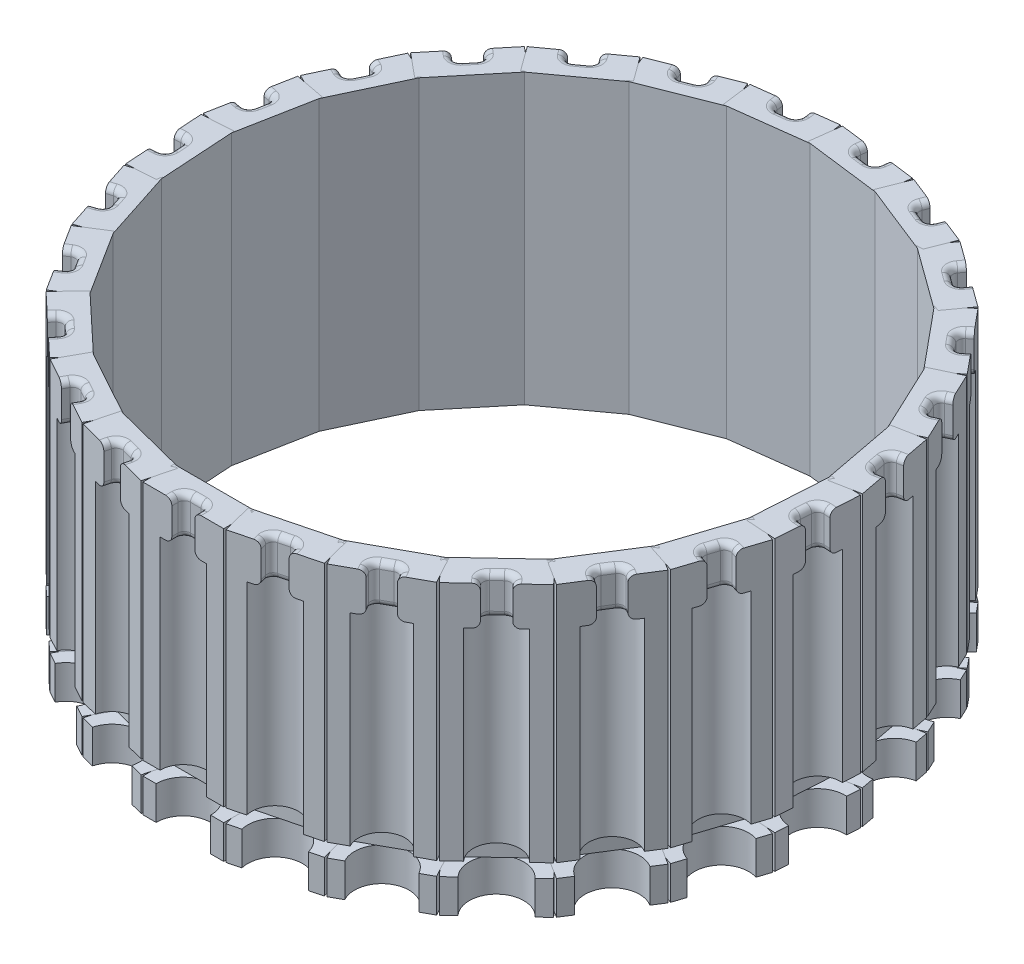
SolidWorks part; units mm, degrees
material "Plain Carbon Steel"
ref_plane "Front Plane" through (0, 0, 0) normal (1, 0, 0) x (0, 1, 0)
ref_plane "Top Plane" through (0, 0, 0) normal (0, 0, 1) x (0, 1, 0)
ref_plane "Right Plane" through (0, 0, 0) normal (0, 1, 0) x (-1, 0, 0)
other "Center of Mass"
sketch "Sketch1" plane through (0, 0, 0) normal (0, 0, 1) x (0, 1, 0)
  line L1 (-75, -150) -> (75, -150)
  line L2 (-75, -150) -> (-75, 150)
  line L3 (-75, 150) -> (75, 150)
  line L4 (75, -150) -> (75, 150)
  line L5 (-75, -150) -> (75, 150) construction
  line L6 (-75, 150) -> (75, -150) construction
  point P0 (0, 0)
  dimension "D1" = 300
  dimension "D2" = 150
extrude "Boss-Extrude1" add sketch "Sketch1" along normal blind 10
sketch "flange slit" plane through (0, 0, 10) normal (0, 0, 1) x (1, 0, 0)
  line L0 (0, 75) -> (0, -75) construction
  line L1 (150, 75) -> (-150, 75) construction
  line L2 (-150, -75) -> (150, -75) construction
  line L3 (-124, 0) -> (150, 0) construction
  line L5 (150, -75) -> (150, 75) construction
  line L6 (-70.7884, -63.1) -> (-70.7884, -60.9) construction
  line L7 (-150, 75) -> (-124, 75) construction
  line L9 (-150, -75) -> (-124, -75) construction
  line L11 (-70.7884, -63.1) -> (-70.7884, -62) construction
  line L12 (-150, -59.8) -> (-124, -59.8)
  line L13 (-150, -59.8) -> (-150, -64.2)
  line L14 (-150, -64.2) -> (-124, -64.2)
  line L19 (-124, -59.8) -> (-124, -64.2)
  line L20 (-150, -59.8) -> (-124, -64.2) construction
  line L21 (-150, -64.2) -> (-124, -59.8) construction
  line L26 (-70.7884, -62) -> (-150, -62) construction
  point P8 (-137, -62)
  dimension "D1" = 26
  dimension "D2" = 2.2
extrude "Flange Slot" cut sketch "flange slit" against normal blind 8
sketch "Sketch3" plane through (0, 0, 10) normal (0, 0, 1) x (1, 0, 0)
  line L0 (-150, -75) -> (150, -75) construction
  line L1 (-150, 75) -> (-124, 75) construction
  line L2 (-150, 75) -> (-150, -75) construction
  line L3 (-150, -75) -> (-124, -75) construction
  line L4 (-124, 75) -> (-124, -75) construction
  line L5 (-150, 75) -> (-124, -75) construction
  line L6 (-150, -75) -> (-124, 75) construction
  line L7 (-124, -64.2) -> (-124, -59.8) construction
  line L8 (-124, -59.8) -> (-150, -59.8) construction
  line L9 (-144.5, -59.8) -> (-129.5, -59.8)
  line L10 (-144.5, -59.8) -> (-144.5, 5.2)
  line L11 (-144.5, 5.2) -> (-129.5, 5.2)
  line L12 (-129.5, -59.8) -> (-129.5, 5.2)
  line L13 (-144.5, -59.8) -> (-129.5, 5.2) construction
  line L14 (-144.5, 5.2) -> (-129.5, -59.8) construction
  line L15 (-137, 75) -> (-137, -59.8) construction
  line L16 (-137, 5.2) -> (-137, -59.8)
  line L18 (-144.5, 5.2) -> (-137, 5.2)
  line L19 (-144.5, 5.2) -> (-144.5, -59.8)
  line L20 (-144.5, -59.8) -> (-137, -59.8)
  line L21 (-137, 5.2) -> (-137, -59.8)
  line L22 (-144.5, 5.2) -> (-137, -59.8) construction
  line L23 (-144.5, -59.8) -> (-137, 5.2) construction
  point P4 (-137, 0)
  point P14 (-137, -27.3)
  point P23 (-140.75, -27.3)
  dimension "D1" = 65
  dimension "D2" = 15
revolve "Syringe Body Slot" cut sketch "Sketch3" angle 360 about L15 region at (-140.75, -27.3, 10)
sketch "Sketch6" plane through (0, 0, 10) normal (0, 0, 1) x (0, -1, 0)
  line L0 (75, 150) -> (-75, 150) construction
  line L1 (-75, -150) -> (-17.7492, -150)
  line L2 (-75, -150) -> (-75, 150)
  line L3 (-75, 150) -> (-17.7492, 150)
  line L4 (-17.7492, -150) -> (-17.7492, 150)
  line L5 (-75, -150) -> (-17.7492, 150) construction
  line L6 (-75, 150) -> (-17.7492, -150) construction
  point P4 (-46.3746, 0)
extrude "Cut-Extrude2" cut sketch "Sketch6" against normal through all
sketch "Sketch7" plane through (0, 0, 10) normal (0, 0, 1) x (1, 0, 0)
  line L0 (-150, -64.2) -> (-124, -64.2) construction
  line L1 (-137, -64.2) -> (-145.7782, -64.2)
  line L2 (-137, -64.2) -> (-137, -75)
  line L3 (-137, -75) -> (-145.7782, -75)
  line L4 (-145.7782, -64.2) -> (-145.7782, -75)
  line L5 (-137, -64.2) -> (-145.7782, -75) construction
  line L6 (-137, -75) -> (-145.7782, -64.2) construction
  line L7 (-150, -75) -> (150, -75) construction
  point P4 (-141.3891, -69.6)
revolve "Plunger Slot" cut sketch "Sketch7" angle 360 about L2
sketch "Sketch8" plane through (0, 0, 10) normal (0, 0, 1) x (1, 0, 0)
  line L0 (-144.5, 5.2) -> (-129.5, 5.2) construction
  line L1 (-140.7, -7.3492) -> (-133.3, -7.3492)
  line L2 (-140.7, -7.3492) -> (-140.7, 17.7492)
  line L3 (-140.7, 17.7492) -> (-133.3, 17.7492)
  line L4 (-133.3, -7.3492) -> (-133.3, 17.7492)
  line L5 (-140.7, -7.3492) -> (-133.3, 17.7492) construction
  line L6 (-140.7, 17.7492) -> (-133.3, -7.3492) construction
  line L7 (-150, 17.7492) -> (150, 17.7492) construction
  point P0 (-137, 5.2)
  dimension "D1" = 7.4
extrude "Needle Slot" cut sketch "Sketch8" against normal blind 4
fillet "Fillet1" radius 2 8 edges at (-140.7, 17.7492, 8) (-140.7, 5.2, 8) (-133.3, 17.7492, 8) (-133.3, 5.2, 8) (-140.7, 11.4746, 6) (-137, 17.7492, 6) (-133.3, 11.4746, 6) (-137, 5.2, 6)
sketch "Sketch10" plane through (0, 0, 0) normal (1, 0, 0) x (0, 1, 0)
  line L0 (-79.9189, -95.2695) -> (22.3591, -95.2695) construction
ref_axis "Axis1" through (0, -79.9189, -95.2695) along (0, 1, 0)
sketch "Sketch11" plane through (0, 0, 10) normal (0, 0, 1) x (1, 0, 0)
  line L0 (-128.2218, -75) -> (150, -75) construction
  line L1 (-124, -75) -> (150, -75)
  line L2 (-124, -75) -> (-124, 17.7492)
  line L3 (-124, 17.7492) -> (150, 17.7492)
  line L4 (150, -75) -> (150, 17.7492)
  line L5 (-124, -75) -> (150, 17.7492) construction
  line L6 (-124, 17.7492) -> (150, -75) construction
  point P4 (13, -28.6254)
extrude "Cut-Extrude3" cut sketch "Sketch11" against normal through all
sketch "Sketch13" plane through (0, 0, 0) normal (0, 0, -1) x (1, 0, 0)
  line L0 (-137, 75) -> (-137, -17.7492) construction
  line L1 (-150, 75) -> (-124, 75) construction
  line L2 (-150, -17.7492) -> (-124, -17.7492) construction
ref_plane "Plane1" through (-137, 0, 0) normal (-1, 0, 0) x (0, 1, 0)
sketch "Sketch15" plane through (-137, 0, 0) normal (-1, 0, 0) x (0, 1, 0)
  line L0 (-78.6799, 95.4838) -> (22.5386, 95.4838)
ref_axis "Axis2" through (-137, -78.6799, -95.4838) along (0, 1, 0)
pattern_circular "CirPattern2" count 25 over 360 about axis through (-137, -78.6799, -95.4838) along (0, 1, 0) of bodies 115
sketch "Sketch16" plane through (0, 0, 0) normal (0, 1, 0) x (-1, 0, 0)
  circle A0 centre (137, -95.4838) radius 95.4838
ref_plane "Plane2" through (0, 0, 0) normal (0, 1, 0) x (-1, 0, 0)
ref_plane "Plane3" through (0, 0, 0) normal (0, -0.7071, -0.7071) x (0, 0.7071, -0.7071)
